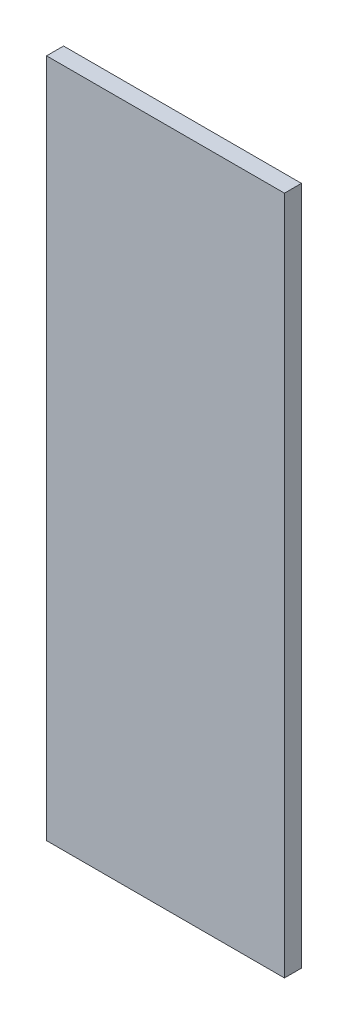
SolidWorks part; units mm, degrees
ref_plane "정면" through (0, 0, 0) normal (0, 0, 1) x (1, 0, 0)
ref_plane "윗면" through (0, 0, 0) normal (0, 1, 0) x (1, 0, 0)
ref_plane "우측면" through (0, 0, 0) normal (1, 0, 0) x (0, 0, -1)
sketch "스케치1" plane through (0, 0, 0) normal (0, 0, 1) x (1, 0, 0)
  line L1 (-50, 100) -> (50, 100)
  line L2 (-50, 100) -> (-50, -100)
  line L3 (-50, -100) -> (50, -100)
  line L4 (50, 100) -> (50, -100)
  line L5 (-50, 100) -> (50, -100) construction
  line L6 (-50, -100) -> (50, 100) construction
  point P0 (0, 0)
  dimension "D1" = 100
  dimension "D2" = 200
extrude "보스-돌출1" add sketch "스케치1" along normal blind 5
sketch "스케치3" plane through (0, 0, 0) normal (0, 0, -1) x (-1, 0, 0)
  text T0 "front"
extrude "컷-돌출2" cut sketch "스케치3" against normal blind 0.001
ref_plane "평면1" through (0, 0, -5) normal (0, 0, -1) x (-1, 0, 0)
sketch "스케치13" plane through (0, 0, 5) normal (0, 0, 1) x (1, 0, 0)
  line L0 (-50, -100) -> (50, -100) construction
  line L1 (50, 100) -> (40, 100)
  line L2 (50, 100) -> (50, -100)
  line L3 (50, -100) -> (40, -100)
  line L4 (40, 100) -> (40, -100)
  line L5 (0, -2.75) -> (0, 2.75) construction
  line L6 (-40, 100) -> (-40, -100)
  line L7 (-50, -100) -> (-40, -100)
  line L8 (-50, 100) -> (-50, -100)
  line L9 (-50, 100) -> (-40, 100)
  dimension "D1" = 10
extrude "컷-돌출4" cut sketch "스케치13" against normal blind 10
sketch "스케치14" plane through (0, 0, 5) normal (0, 0, 1) x (1, 0, 0)
  line L0 (-40, -100) -> (40, -100) construction
  line L1 (40, 100) -> (30, 100)
  line L2 (40, 100) -> (40, -100)
  line L3 (40, -100) -> (30, -100)
  line L4 (30, 100) -> (30, -100)
  dimension "D1" = 10
extrude "컷-돌출5" cut sketch "스케치14" against normal blind 10
